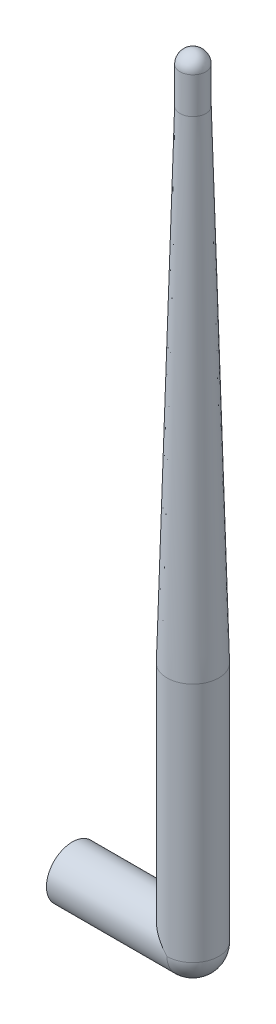
SolidWorks part; units mm, degrees
material "Rubber"
ref_plane "Front Plane" through (0, 0, 0) normal (0, 0, 1) x (1, 0, 0)
ref_plane "Top Plane" through (0, 0, 0) normal (0, 1, 0) x (1, 0, 0)
ref_plane "Right Plane" through (0, 0, 0) normal (1, 0, 0) x (0, 0, -1)
sketch "Sketch1" plane through (0, 0, 0) normal (1, 0, 0) x (0, 0, -1)
  circle A0 centre (0, 0) radius 5.461
  dimension "D1" = 10.922
extrude "Boss-Extrude1" add sketch "Sketch1" along normal blind 25.4
sketch "Sketch2" plane through (0, 0, 0) normal (-1, 0, 0) x (0, 0, 1)
  circle A0 centre (0, 0) radius 4.191
  dimension "D1" = 8.382
extrude "Cut-Extrude1" cut sketch "Sketch2" against normal blind 7.62
sketch "Sketch3" plane through (0, 0, 0) normal (0, 1, 0) x (1, 0, 0)
  line L0 (25.4, -5.461) -> (25.4, 5.461) construction
  circle A0 centre (25.4, 0) radius 5.461
extrude "Boss-Extrude2" add sketch "Sketch3" along normal blind 50.8
sketch "Sketch7" plane through (25.4, 0, 0) normal (1, 0, 0) x (0, 0, -1)
  line L0 (5.461, 0) -> (-5.461, 0) construction
  line L1 (5.461, 0) -> (-5.461, 0)
  arc A0 (-5.461, 0) -> (5.461, 0) centre (0, 0) ccw construction
  arc A1 (-5.461, 0) -> (5.461, 0) centre (0, 0) ccw
revolve "Revolve2" add sketch "Sketch7" angle 90 about L1
ref_plane "Plane1" through (0, 152.4, 0) normal (0, 1, 0) x (1, 0, 0)
sketch "Sketch8" plane through (0, 152.4, 0) normal (0, 1, 0) x (1, 0, 0)
  circle A2 centre (25.4, 0) radius 2.7305
  arc A3 (25.4, 2.7305) -> (25.4, -2.7305) centre (25.4, 0) ccw
loft "Loft2" add section face at (25.4, 50.8, 5.461) section "Sketch8" connector at (24.1318, 50.8, -5.3117) connector at (24.7122, 152.4, -2.6425)
sketch "Sketch9" plane through (0, 152.4, 0) normal (0, 1, 0) x (1, 0, 0)
  circle A0 centre (25.4, 0) radius 2.7305
extrude "Boss-Extrude3" add sketch "Sketch9" along normal blind 7.62
sketch "Sketch10" plane through (0, 160.02, 0) normal (0, 1, 0) x (1, 0, 0)
  line L0 (25.4, 2.7305) -> (25.4, -2.7305)
  arc A0 (25.4, -2.7305) -> (25.4, 2.7305) centre (25.4, 0) ccw
revolve "Revolve3" add sketch "Sketch10" angle 180 about L0
